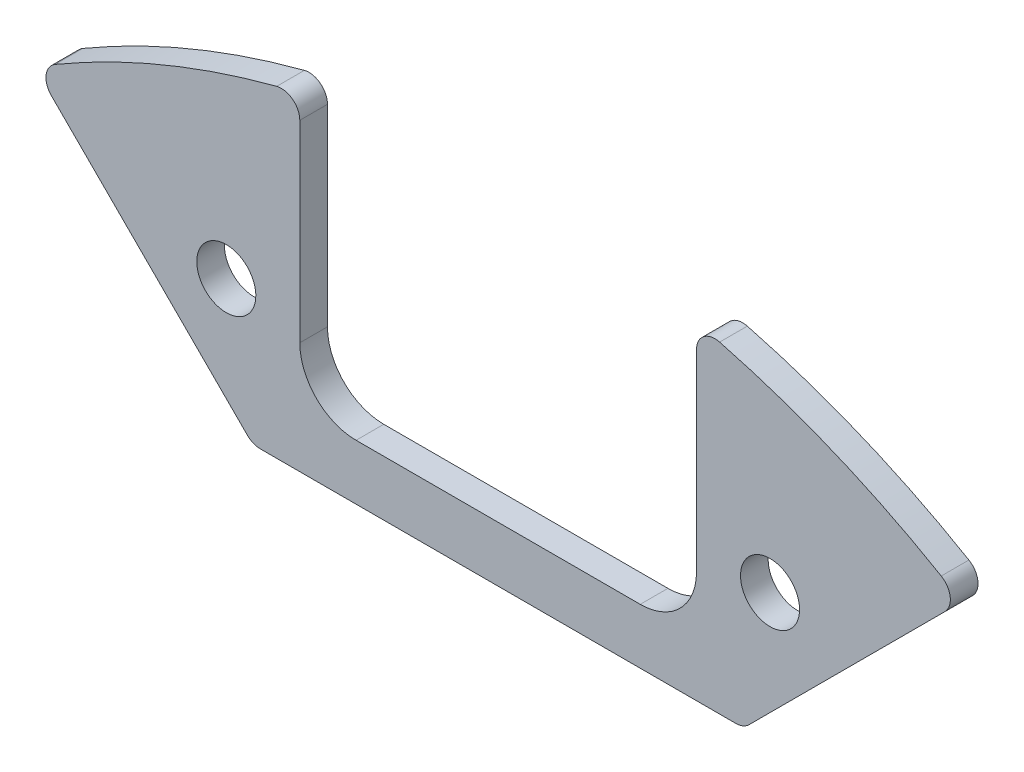
SolidWorks part; units mm, degrees
material "5052-H34"
ref_plane "正面" through (0, 0, 0) normal (0, 0, 1) x (1, 0, 0)
ref_plane "平面" through (0, 0, 0) normal (0, 1, 0) x (1, 0, 0)
ref_plane "右側面" through (0, 0, 0) normal (1, 0, 0) x (0, 0, -1)
sketch "ｽｹｯﾁ1" plane through (0, 0, 0) normal (0, 0, 1) x (1, 0, 0)
  circle A0 centre (0, 0) radius 47.5
  dimension "D1" = 95
extrude "ﾎﾞｽ - 押し出し1" add sketch "ｽｹｯﾁ1" along normal blind 1.5
sketch "ｽｹｯﾁ2" plane through (0, 0, 1.5) normal (0, 0, 1) x (1, 0, 0)
  line L0 (0, 0) -> (0, 47.5) construction
  line L1 (-10.75, 43.525) -> (-10.75, 52.5)
  line L2 (-10.75, 31.5) -> (10.75, 31.5)
  line L3 (-10.75, 31.5) -> (-10.75, 40.475)
  line L4 (-10.75, 52.5) -> (10.75, 52.5)
  line L5 (10.75, 31.5) -> (10.75, 40.475)
  line L6 (-10.75, 31.5) -> (10.75, 52.5) construction
  line L7 (-10.75, 52.5) -> (10.75, 31.5) construction
  line L8 (-13, 43.525) -> (-10.75, 43.525)
  line L9 (-13, 43.525) -> (-13, 40.475)
  line L10 (-13, 40.475) -> (-10.75, 40.475)
  line L11 (13, 43.525) -> (13, 40.475)
  line L12 (-13, 43.525) -> (13, 40.475) construction
  line L13 (-13, 40.475) -> (13, 43.525) construction
  line L14 (10.75, 43.525) -> (10.75, 52.5)
  line L15 (10.75, 43.525) -> (13, 43.525)
  line L17 (10.75, 40.475) -> (13, 40.475)
  circle A0 centre (0, 0) radius 47.5 construction
  point P5 (0, 42)
  point P10 (0, 42)
  dimension "D1" = 42
  dimension "D2" = 21.5
  dimension "D3" = 21
  dimension "D4" = 3.05
  dimension "D5" = 26
extrude "ｶｯﾄ - 押し出し1" cut sketch "ｽｹｯﾁ2" against normal through all
sketch "ｽｹｯﾁ3" plane through (0, 0, 1.5) normal (0, 0, 1) x (1, 0, 0)
  line L1 (-8.8388, -8.8388) -> (8.8388, -8.8388) construction
  line L2 (-8.8388, -8.8388) -> (-8.8388, 8.8388) construction
  line L3 (-8.8388, 8.8388) -> (8.8388, 8.8388) construction
  line L4 (8.8388, -8.8388) -> (8.8388, 8.8388) construction
  line L5 (-8.8388, -8.8388) -> (8.8388, 8.8388) construction
  line L6 (-8.8388, 8.8388) -> (8.8388, -8.8388) construction
  circle A0 centre (0, 0) radius 3.1
  circle A1 centre (0, 0) radius 6.5 construction
  circle A2 centre (0, 6.5) radius 1.6
  circle A3 centre (6.5, 0) radius 1.6
  circle A4 centre (0, -6.5) radius 1.6
  circle A5 centre (-6.5, 0) radius 1.6
  circle A6 centre (0, 0) radius 12.5 construction
  circle A7 centre (8.8388, 8.8388) radius 1.6
  circle A8 centre (8.8388, -8.8388) radius 1.6
  circle A9 centre (-8.8388, -8.8388) radius 1.6
  circle A10 centre (-8.8388, 8.8388) radius 1.6
  dimension "D1" = 6.2
  dimension "D2" = 13
  dimension "D3" = 3.2
  dimension "D5" = 25
  dimension "D6" = 3.2
  dimension "D4" = 4
  dimension "D7" = 4
extrude "ｶｯﾄ - 押し出し2" cut sketch "ｽｹｯﾁ3" against normal through all and the other way through all
sketch "ｽｹｯﾁ4" plane through (0, 0, 1.5) normal (0, 0, 1) x (1, 0, 0)
  line L0 (0, 31.5) -> (0, 0) construction
  line L1 (-10.75, 31.5) -> (10.75, 31.5) construction
  line L2 (0, 0) -> (14.7333, 35.5694) construction
  circle A0 centre (0, 0) radius 22.5 construction
  circle A1 centre (0, 0) radius 38.5 construction
  circle A2 centre (14.7333, 35.5694) radius 1.6
  circle A3 centre (8.6104, 20.7873) radius 1.6
  dimension "D1" = 45
  dimension "D2" = 77
  dimension "D4" = 3.2
  dimension "D3" = 22.5
extrude "ｶｯﾄ - 押し出し3" cut sketch "ｽｹｯﾁ4" against normal through all
sketch "ｽｹｯﾁ5" plane through (0, 0, 1.5) normal (0, 0, 1) x (1, 0, 0)
  line L0 (0, 0) -> (14.7333, 35.5694) construction
  line L1 (-10.75, 31.5) -> (10.75, 31.5) construction
  line L2 (-10.75, 31.5) -> (10.75, 31.5) construction
  line L3 (-7.1883, 26.5) -> (7.1883, 26.5)
  line L4 (-3.3281, 17.1806) -> (-7.1883, 26.5)
  line L5 (0, 31.5) -> (0, 0) construction
  line L6 (-10.75, 26.5) -> (10.75, 26.5) construction
  line L9 (-3.3281, 17.1806) -> (3.3281, 17.1806)
  line L10 (3.3281, 17.1806) -> (7.1883, 26.5)
  circle A0 centre (0, 0) radius 17.5 construction
  dimension "D3" = 35
  dimension "D2" = 7
  dimension "D1" = 5
extrude "ｶｯﾄ - 押し出し4" cut sketch "ｽｹｯﾁ5" against normal through all and the other way through all
fillet "ﾌｨﾚｯﾄ1" radius 1 6 edges at (-3.3281, 17.1806, 0.75) (3.3281, 17.1806, 0.75) (7.1883, 26.5, 0.75) (-7.1883, 26.5, 0.75) (10.75, 46.2676, 0.75) (-10.75, 46.2676, 0.75)
fillet "ﾌｨﾚｯﾄ2" radius 0.2 4 edges at (13, 43.525, 0.75) (13, 40.475, 0.75) (-13, 43.525, 0.75) (-13, 40.475, 0.75)
fillet "ﾌｨﾚｯﾄ3" radius 3.05 2 edges at (10.75, 31.5, 0.75) (-10.75, 31.5, 0.75)
ref_axis "軸1" through (0, 0, 0) along (0, 0, 1)
pattern_circular "円形ﾊﾟﾀｰﾝ1" count 8 over 360 about axis through (0, 0, 0) along (0, 0, 1) of "ｶｯﾄ - 押し出し1", "ﾌｨﾚｯﾄ1", "ｶｯﾄ - 押し出し4", "ｶｯﾄ - 押し出し3", "ﾌｨﾚｯﾄ2", "ﾌｨﾚｯﾄ3"
sketch "ｽｹｯﾁ6" plane through (0, 0, 1.5) normal (0, 0, 1) x (1, 0, 0)
  line L0 (7.7, 28.5) -> (-7.7, 28.5)
  line L1 (-7.7, 28.5) -> (-13.2972, 28.5)
  line L2 (-13.2972, 28.5) -> (-21.0187, 36.2215)
  line L3 (7.7, 28.5) -> (13.2972, 28.5)
  line L4 (25.5973, 14.7078) -> (14.7078, 25.5973)
  line L7 (28.5, -7.7) -> (28.5, 7.7)
  line L10 (14.7078, -25.5973) -> (25.5973, -14.7078)
  line L13 (-7.7, -28.5) -> (7.7, -28.5)
  line L16 (-25.5973, -14.7078) -> (-14.7078, -25.5973)
  line L19 (-28.5, 7.7) -> (-28.5, -7.7)
  line L22 (-14.7078, 25.5973) -> (-25.5973, 14.7078)
  line L23 (13.2972, 28.5) -> (21.0187, 36.2215)
  line L88 (39.4148, 24.212) -> (38.3782, 23.1754)
  line L89 (38.3782, 23.1754) -> (39.8278, 21.7259)
  line L90 (39.8278, 21.443) -> (37.954, 19.5692)
  line L91 (37.6711, 19.5692) -> (36.2215, 21.0187)
  line L92 (36.2215, 21.0187) -> (32.0319, 16.8291)
  line L93 (27.7186, 16.8291) -> (16.8291, 27.7186)
  line L94 (16.8291, 32.0319) -> (21.0187, 36.2215)
  line L95 (21.0187, 36.2215) -> (19.5692, 37.6711)
  line L96 (19.5692, 37.954) -> (21.443, 39.8278)
  line L97 (21.7259, 39.8278) -> (23.1754, 38.3782)
  line L98 (23.1754, 38.3782) -> (24.212, 39.4148)
  line L99 (10.75, 44.991) -> (10.75, 43.525)
  line L100 (10.75, 43.525) -> (12.8, 43.525)
  line L101 (13, 43.325) -> (13, 40.675)
  line L102 (12.8, 40.475) -> (10.75, 40.475)
  line L103 (10.75, 40.475) -> (10.75, 34.55)
  line L104 (7.7, 31.5) -> (-7.7, 31.5)
  line L105 (-10.75, 34.55) -> (-10.75, 40.475)
  line L106 (-10.75, 40.475) -> (-12.8, 40.475)
  line L107 (-13, 40.675) -> (-13, 43.325)
  line L108 (-12.8, 43.525) -> (-10.75, 43.525)
  line L109 (-10.75, 43.525) -> (-10.75, 44.991)
  line L110 (-24.212, 39.4148) -> (-23.1754, 38.3782)
  line L111 (-23.1754, 38.3782) -> (-21.7259, 39.8278)
  line L112 (-21.443, 39.8278) -> (-19.5692, 37.954)
  line L113 (-19.5692, 37.6711) -> (-21.0187, 36.2215)
  line L114 (-21.0187, 36.2215) -> (-16.8291, 32.0319)
  line L115 (-16.8291, 27.7186) -> (-27.7186, 16.8291)
  line L116 (-32.0319, 16.8291) -> (-36.2215, 21.0187)
  line L117 (-36.2215, 21.0187) -> (-37.6711, 19.5692)
  line L118 (-37.954, 19.5692) -> (-39.8278, 21.443)
  line L119 (-39.8278, 21.7259) -> (-38.3782, 23.1754)
  line L120 (-38.3782, 23.1754) -> (-39.4148, 24.212)
  line L121 (-44.991, 10.75) -> (-43.525, 10.75)
  line L122 (-43.525, 10.75) -> (-43.525, 12.8)
  line L123 (-43.325, 13) -> (-40.675, 13)
  line L124 (-40.475, 12.8) -> (-40.475, 10.75)
  line L125 (-40.475, 10.75) -> (-34.55, 10.75)
  line L126 (-31.5, 7.7) -> (-31.5, -7.7)
  line L127 (-34.55, -10.75) -> (-40.475, -10.75)
  line L128 (-40.475, -10.75) -> (-40.475, -12.8)
  line L129 (-40.675, -13) -> (-43.325, -13)
  line L130 (-43.525, -12.8) -> (-43.525, -10.75)
  line L131 (-43.525, -10.75) -> (-44.991, -10.75)
  line L132 (-39.4148, -24.212) -> (-38.3782, -23.1754)
  line L133 (-38.3782, -23.1754) -> (-39.8278, -21.7259)
  line L134 (-39.8278, -21.443) -> (-37.954, -19.5692)
  line L135 (-37.6711, -19.5692) -> (-36.2215, -21.0187)
  line L136 (-36.2215, -21.0187) -> (-32.0319, -16.8291)
  line L137 (-27.7186, -16.8291) -> (-16.8291, -27.7186)
  line L138 (-16.8291, -32.0319) -> (-21.0187, -36.2215)
  line L139 (-21.0187, -36.2215) -> (-19.5692, -37.6711)
  line L140 (-19.5692, -37.954) -> (-21.443, -39.8278)
  line L141 (-21.7259, -39.8278) -> (-23.1754, -38.3782)
  line L142 (-23.1754, -38.3782) -> (-24.212, -39.4148)
  line L143 (-10.75, -44.991) -> (-10.75, -43.525)
  line L144 (-10.75, -43.525) -> (-12.8, -43.525)
  line L145 (-13, -43.325) -> (-13, -40.675)
  line L146 (-12.8, -40.475) -> (-10.75, -40.475)
  line L147 (-10.75, -40.475) -> (-10.75, -34.55)
  line L148 (-7.7, -31.5) -> (7.7, -31.5)
  line L149 (10.75, -34.55) -> (10.75, -40.475)
  line L150 (10.75, -40.475) -> (12.8, -40.475)
  line L151 (13, -40.675) -> (13, -43.325)
  line L152 (12.8, -43.525) -> (10.75, -43.525)
  line L153 (10.75, -43.525) -> (10.75, -44.991)
  line L154 (24.212, -39.4148) -> (23.1754, -38.3782)
  line L155 (23.1754, -38.3782) -> (21.7259, -39.8278)
  line L156 (21.443, -39.8278) -> (19.5692, -37.954)
  line L157 (19.5692, -37.6711) -> (21.0187, -36.2215)
  line L158 (21.0187, -36.2215) -> (16.8291, -32.0319)
  line L159 (16.8291, -27.7186) -> (27.7186, -16.8291)
  line L160 (32.0319, -16.8291) -> (36.2215, -21.0187)
  line L161 (36.2215, -21.0187) -> (37.6711, -19.5692)
  line L162 (37.954, -19.5692) -> (39.8278, -21.443)
  line L163 (39.8278, -21.7259) -> (38.3782, -23.1754)
  line L164 (38.3782, -23.1754) -> (39.4148, -24.212)
  line L165 (44.991, -10.75) -> (43.525, -10.75)
  line L166 (43.525, -10.75) -> (43.525, -12.8)
  line L167 (43.325, -13) -> (40.675, -13)
  line L168 (40.475, -12.8) -> (40.475, -10.75)
  line L169 (40.475, -10.75) -> (34.55, -10.75)
  line L170 (31.5, -7.7) -> (31.5, 7.7)
  line L171 (34.55, 10.75) -> (40.475, 10.75)
  line L172 (40.475, 10.75) -> (40.475, 12.8)
  line L173 (40.675, 13) -> (43.325, 13)
  line L174 (43.525, 12.8) -> (43.525, 10.75)
  line L175 (43.525, 10.75) -> (44.991, 10.75)
  line L176 (39.4148, 24.212) -> (38.3782, 23.1754)
  line L177 (38.3782, 23.1754) -> (39.8278, 21.7259)
  line L178 (39.8278, 21.443) -> (37.954, 19.5692)
  line L179 (37.6711, 19.5692) -> (36.2215, 21.0187)
  line L180 (36.2215, 21.0187) -> (32.0319, 16.8291)
  line L181 (27.7186, 16.8291) -> (16.8291, 27.7186)
  line L182 (16.8291, 32.0319) -> (21.0187, 36.2215)
  line L183 (21.0187, 36.2215) -> (19.5692, 37.6711)
  line L184 (19.5692, 37.954) -> (21.443, 39.8278)
  line L185 (21.7259, 39.8278) -> (23.1754, 38.3782)
  line L186 (23.1754, 38.3782) -> (24.212, 39.4148)
  line L187 (10.75, 44.991) -> (10.75, 43.525)
  line L188 (10.75, 43.525) -> (12.8, 43.525)
  line L189 (13, 43.325) -> (13, 40.675)
  line L190 (12.8, 40.475) -> (10.75, 40.475)
  line L191 (10.75, 40.475) -> (10.75, 34.55)
  line L192 (7.7, 31.5) -> (-7.7, 31.5)
  line L193 (-10.75, 34.55) -> (-10.75, 40.475)
  line L194 (-10.75, 40.475) -> (-12.8, 40.475)
  line L195 (-13, 40.675) -> (-13, 43.325)
  line L196 (-12.8, 43.525) -> (-10.75, 43.525)
  line L197 (-10.75, 43.525) -> (-10.75, 44.991)
  line L198 (-24.212, 39.4148) -> (-23.1754, 38.3782)
  line L199 (-23.1754, 38.3782) -> (-21.7259, 39.8278)
  line L200 (-21.443, 39.8278) -> (-19.5692, 37.954)
  line L201 (-19.5692, 37.6711) -> (-21.0187, 36.2215)
  line L202 (-21.0187, 36.2215) -> (-16.8291, 32.0319)
  line L203 (-16.8291, 27.7186) -> (-27.7186, 16.8291)
  line L204 (-32.0319, 16.8291) -> (-36.2215, 21.0187)
  line L205 (-36.2215, 21.0187) -> (-37.6711, 19.5692)
  line L206 (-37.954, 19.5692) -> (-39.8278, 21.443)
  line L207 (-39.8278, 21.7259) -> (-38.3782, 23.1754)
  line L208 (-38.3782, 23.1754) -> (-39.4148, 24.212)
  line L209 (-44.991, 10.75) -> (-43.525, 10.75)
  line L210 (-43.525, 10.75) -> (-43.525, 12.8)
  line L211 (-43.325, 13) -> (-40.675, 13)
  line L212 (-40.475, 12.8) -> (-40.475, 10.75)
  line L213 (-40.475, 10.75) -> (-34.55, 10.75)
  line L214 (-31.5, 7.7) -> (-31.5, -7.7)
  line L215 (-34.55, -10.75) -> (-40.475, -10.75)
  line L216 (-40.475, -10.75) -> (-40.475, -12.8)
  line L217 (-40.675, -13) -> (-43.325, -13)
  line L218 (-43.525, -12.8) -> (-43.525, -10.75)
  line L219 (-43.525, -10.75) -> (-44.991, -10.75)
  line L220 (-39.4148, -24.212) -> (-38.3782, -23.1754)
  line L221 (-38.3782, -23.1754) -> (-39.8278, -21.7259)
  line L222 (-39.8278, -21.443) -> (-37.954, -19.5692)
  line L223 (-37.6711, -19.5692) -> (-36.2215, -21.0187)
  line L224 (-36.2215, -21.0187) -> (-32.0319, -16.8291)
  line L225 (-27.7186, -16.8291) -> (-16.8291, -27.7186)
  line L226 (-16.8291, -32.0319) -> (-21.0187, -36.2215)
  line L227 (-21.0187, -36.2215) -> (-19.5692, -37.6711)
  line L228 (-19.5692, -37.954) -> (-21.443, -39.8278)
  line L229 (-21.7259, -39.8278) -> (-23.1754, -38.3782)
  line L230 (-23.1754, -38.3782) -> (-24.212, -39.4148)
  line L231 (-10.75, -44.991) -> (-10.75, -43.525)
  line L232 (-10.75, -43.525) -> (-12.8, -43.525)
  line L233 (-13, -43.325) -> (-13, -40.675)
  line L234 (-12.8, -40.475) -> (-10.75, -40.475)
  line L235 (-10.75, -40.475) -> (-10.75, -34.55)
  line L236 (-7.7, -31.5) -> (7.7, -31.5)
  line L237 (10.75, -34.55) -> (10.75, -40.475)
  line L238 (10.75, -40.475) -> (12.8, -40.475)
  line L239 (13, -40.675) -> (13, -43.325)
  line L240 (12.8, -43.525) -> (10.75, -43.525)
  line L241 (10.75, -43.525) -> (10.75, -44.991)
  line L242 (24.212, -39.4148) -> (23.1754, -38.3782)
  line L243 (23.1754, -38.3782) -> (21.7259, -39.8278)
  line L244 (21.443, -39.8278) -> (19.5692, -37.954)
  line L245 (19.5692, -37.6711) -> (21.0187, -36.2215)
  line L246 (21.0187, -36.2215) -> (16.8291, -32.0319)
  line L247 (16.8291, -27.7186) -> (27.7186, -16.8291)
  line L248 (32.0319, -16.8291) -> (36.2215, -21.0187)
  line L249 (36.2215, -21.0187) -> (37.6711, -19.5692)
  line L250 (37.954, -19.5692) -> (39.8278, -21.443)
  line L251 (39.8278, -21.7259) -> (38.3782, -23.1754)
  line L252 (38.3782, -23.1754) -> (39.4148, -24.212)
  line L253 (44.991, -10.75) -> (43.525, -10.75)
  line L254 (43.525, -10.75) -> (43.525, -12.8)
  line L255 (43.325, -13) -> (40.675, -13)
  line L256 (40.475, -12.8) -> (40.475, -10.75)
  line L257 (40.475, -10.75) -> (34.55, -10.75)
  line L258 (31.5, -7.7) -> (31.5, 7.7)
  line L259 (34.55, 10.75) -> (40.475, 10.75)
  line L260 (40.475, 10.75) -> (40.475, 12.8)
  line L261 (40.675, 13) -> (43.325, 13)
  line L262 (43.525, 12.8) -> (43.525, 10.75)
  line L263 (43.525, 10.75) -> (44.991, 10.75)
  arc A72 (45.9585, 12.0027) -> (40.9848, 24.0104) centre (0, 0) ccw
  arc A73 (40.9848, 24.0104) -> (39.4148, 24.212) centre (40.1219, 23.5049) ccw
  arc A74 (39.8278, 21.443) -> (39.8278, 21.7259) centre (39.6864, 21.5844) ccw
  arc A75 (37.6711, 19.5692) -> (37.954, 19.5692) centre (37.8125, 19.7106) ccw
  arc A76 (27.7186, 16.8291) -> (32.0319, 16.8291) centre (29.8753, 18.9858) ccw
  arc A77 (16.8291, 32.0319) -> (16.8291, 27.7186) centre (18.9858, 29.8753) ccw
  arc A78 (19.5692, 37.954) -> (19.5692, 37.6711) centre (19.7106, 37.8125) ccw
  arc A79 (21.7259, 39.8278) -> (21.443, 39.8278) centre (21.5844, 39.6864) ccw
  arc A80 (24.212, 39.4148) -> (24.0104, 40.9848) centre (23.5049, 40.1219) ccw
  arc A81 (24.0104, 40.9848) -> (12.0027, 45.9585) centre (0, 0) ccw
  arc A82 (12.0027, 45.9585) -> (10.75, 44.991) centre (11.75, 44.991) ccw
  arc A83 (13, 43.325) -> (12.8, 43.525) centre (12.8, 43.325) ccw
  arc A84 (12.8, 40.475) -> (13, 40.675) centre (12.8, 40.675) ccw
  arc A85 (7.7, 31.5) -> (10.75, 34.55) centre (7.7, 34.55) ccw
  arc A86 (-10.75, 34.55) -> (-7.7, 31.5) centre (-7.7, 34.55) ccw
  arc A87 (-13, 40.675) -> (-12.8, 40.475) centre (-12.8, 40.675) ccw
  arc A88 (-12.8, 43.525) -> (-13, 43.325) centre (-12.8, 43.325) ccw
  arc A89 (-10.75, 44.991) -> (-12.0027, 45.9585) centre (-11.75, 44.991) ccw
  arc A90 (-12.0027, 45.9585) -> (-24.0104, 40.9848) centre (0, 0) ccw
  arc A91 (-24.0104, 40.9848) -> (-24.212, 39.4148) centre (-23.5049, 40.1219) ccw
  arc A92 (-21.443, 39.8278) -> (-21.7259, 39.8278) centre (-21.5844, 39.6864) ccw
  arc A93 (-19.5692, 37.6711) -> (-19.5692, 37.954) centre (-19.7106, 37.8125) ccw
  arc A94 (-16.8291, 27.7186) -> (-16.8291, 32.0319) centre (-18.9858, 29.8753) ccw
  arc A95 (-32.0319, 16.8291) -> (-27.7186, 16.8291) centre (-29.8753, 18.9858) ccw
  arc A96 (-37.954, 19.5692) -> (-37.6711, 19.5692) centre (-37.8125, 19.7106) ccw
  arc A97 (-39.8278, 21.7259) -> (-39.8278, 21.443) centre (-39.6864, 21.5844) ccw
  arc A98 (-39.4148, 24.212) -> (-40.9848, 24.0104) centre (-40.1219, 23.5049) ccw
  arc A99 (-40.9848, 24.0104) -> (-45.9585, 12.0027) centre (0, 0) ccw
  arc A100 (-45.9585, 12.0027) -> (-44.991, 10.75) centre (-44.991, 11.75) ccw
  arc A101 (-43.325, 13) -> (-43.525, 12.8) centre (-43.325, 12.8) ccw
  arc A102 (-40.475, 12.8) -> (-40.675, 13) centre (-40.675, 12.8) ccw
  arc A103 (-31.5, 7.7) -> (-34.55, 10.75) centre (-34.55, 7.7) ccw
  arc A104 (-34.55, -10.75) -> (-31.5, -7.7) centre (-34.55, -7.7) ccw
  arc A105 (-40.675, -13) -> (-40.475, -12.8) centre (-40.675, -12.8) ccw
  arc A106 (-43.525, -12.8) -> (-43.325, -13) centre (-43.325, -12.8) ccw
  arc A107 (-44.991, -10.75) -> (-45.9585, -12.0027) centre (-44.991, -11.75) ccw
  arc A108 (-45.9585, -12.0027) -> (-40.9848, -24.0104) centre (0, 0) ccw
  arc A109 (-40.9848, -24.0104) -> (-39.4148, -24.212) centre (-40.1219, -23.5049) ccw
  arc A110 (-39.8278, -21.443) -> (-39.8278, -21.7259) centre (-39.6864, -21.5844) ccw
  arc A111 (-37.6711, -19.5692) -> (-37.954, -19.5692) centre (-37.8125, -19.7106) ccw
  arc A112 (-27.7186, -16.8291) -> (-32.0319, -16.8291) centre (-29.8753, -18.9858) ccw
  arc A113 (-16.8291, -32.0319) -> (-16.8291, -27.7186) centre (-18.9858, -29.8753) ccw
  arc A114 (-19.5692, -37.954) -> (-19.5692, -37.6711) centre (-19.7106, -37.8125) ccw
  arc A115 (-21.7259, -39.8278) -> (-21.443, -39.8278) centre (-21.5844, -39.6864) ccw
  arc A116 (-24.212, -39.4148) -> (-24.0104, -40.9848) centre (-23.5049, -40.1219) ccw
  arc A117 (-24.0104, -40.9848) -> (-12.0027, -45.9585) centre (0, 0) ccw
  arc A118 (-12.0027, -45.9585) -> (-10.75, -44.991) centre (-11.75, -44.991) ccw
  arc A119 (-13, -43.325) -> (-12.8, -43.525) centre (-12.8, -43.325) ccw
  arc A120 (-12.8, -40.475) -> (-13, -40.675) centre (-12.8, -40.675) ccw
  arc A121 (-7.7, -31.5) -> (-10.75, -34.55) centre (-7.7, -34.55) ccw
  arc A122 (10.75, -34.55) -> (7.7, -31.5) centre (7.7, -34.55) ccw
  arc A123 (13, -40.675) -> (12.8, -40.475) centre (12.8, -40.675) ccw
  arc A124 (12.8, -43.525) -> (13, -43.325) centre (12.8, -43.325) ccw
  arc A125 (10.75, -44.991) -> (12.0027, -45.9585) centre (11.75, -44.991) ccw
  arc A126 (12.0027, -45.9585) -> (24.0104, -40.9848) centre (0, 0) ccw
  arc A127 (24.0104, -40.9848) -> (24.212, -39.4148) centre (23.5049, -40.1219) ccw
  arc A128 (21.443, -39.8278) -> (21.7259, -39.8278) centre (21.5844, -39.6864) ccw
  arc A129 (19.5692, -37.6711) -> (19.5692, -37.954) centre (19.7106, -37.8125) ccw
  arc A130 (16.8291, -27.7186) -> (16.8291, -32.0319) centre (18.9858, -29.8753) ccw
  arc A131 (32.0319, -16.8291) -> (27.7186, -16.8291) centre (29.8753, -18.9858) ccw
  arc A132 (37.954, -19.5692) -> (37.6711, -19.5692) centre (37.8125, -19.7106) ccw
  arc A133 (39.8278, -21.7259) -> (39.8278, -21.443) centre (39.6864, -21.5844) ccw
  arc A134 (39.4148, -24.212) -> (40.9848, -24.0104) centre (40.1219, -23.5049) ccw
  arc A135 (40.9848, -24.0104) -> (45.9585, -12.0027) centre (0, 0) ccw
  arc A136 (45.9585, -12.0027) -> (44.991, -10.75) centre (44.991, -11.75) ccw
  arc A137 (43.325, -13) -> (43.525, -12.8) centre (43.325, -12.8) ccw
  arc A138 (40.475, -12.8) -> (40.675, -13) centre (40.675, -12.8) ccw
  arc A139 (31.5, -7.7) -> (34.55, -10.75) centre (34.55, -7.7) ccw
  arc A140 (34.55, 10.75) -> (31.5, 7.7) centre (34.55, 7.7) ccw
  arc A141 (40.675, 13) -> (40.475, 12.8) centre (40.675, 12.8) ccw
  arc A142 (43.525, 12.8) -> (43.325, 13) centre (43.325, 12.8) ccw
  arc A143 (44.991, 10.75) -> (45.9585, 12.0027) centre (44.991, 11.75) ccw
  arc A144 (45.9585, 12.0027) -> (40.9848, 24.0104) centre (0, 0) ccw
  arc A145 (40.9848, 24.0104) -> (39.4148, 24.212) centre (40.1219, 23.5049) ccw
  arc A146 (39.8278, 21.443) -> (39.8278, 21.7259) centre (39.6864, 21.5844) ccw
  arc A147 (37.6711, 19.5692) -> (37.954, 19.5692) centre (37.8125, 19.7106) ccw
  arc A148 (27.7186, 16.8291) -> (32.0319, 16.8291) centre (29.8753, 18.9858) ccw
  arc A149 (16.8291, 32.0319) -> (16.8291, 27.7186) centre (18.9858, 29.8753) ccw
  arc A150 (19.5692, 37.954) -> (19.5692, 37.6711) centre (19.7106, 37.8125) ccw
  arc A151 (21.7259, 39.8278) -> (21.443, 39.8278) centre (21.5844, 39.6864) ccw
  arc A152 (24.212, 39.4148) -> (24.0104, 40.9848) centre (23.5049, 40.1219) ccw
  arc A153 (24.0104, 40.9848) -> (12.0027, 45.9585) centre (0, 0) ccw
  arc A154 (12.0027, 45.9585) -> (10.75, 44.991) centre (11.75, 44.991) ccw
  arc A155 (13, 43.325) -> (12.8, 43.525) centre (12.8, 43.325) ccw
  arc A156 (12.8, 40.475) -> (13, 40.675) centre (12.8, 40.675) ccw
  arc A157 (7.7, 31.5) -> (10.75, 34.55) centre (7.7, 34.55) ccw
  arc A158 (-10.75, 34.55) -> (-7.7, 31.5) centre (-7.7, 34.55) ccw
  arc A159 (-13, 40.675) -> (-12.8, 40.475) centre (-12.8, 40.675) ccw
  arc A160 (-12.8, 43.525) -> (-13, 43.325) centre (-12.8, 43.325) ccw
  arc A161 (-10.75, 44.991) -> (-12.0027, 45.9585) centre (-11.75, 44.991) ccw
  arc A162 (-12.0027, 45.9585) -> (-24.0104, 40.9848) centre (0, 0) ccw
  arc A163 (-24.0104, 40.9848) -> (-24.212, 39.4148) centre (-23.5049, 40.1219) ccw
  arc A164 (-21.443, 39.8278) -> (-21.7259, 39.8278) centre (-21.5844, 39.6864) ccw
  arc A165 (-19.5692, 37.6711) -> (-19.5692, 37.954) centre (-19.7106, 37.8125) ccw
  arc A166 (-16.8291, 27.7186) -> (-16.8291, 32.0319) centre (-18.9858, 29.8753) ccw
  arc A167 (-32.0319, 16.8291) -> (-27.7186, 16.8291) centre (-29.8753, 18.9858) ccw
  arc A168 (-37.954, 19.5692) -> (-37.6711, 19.5692) centre (-37.8125, 19.7106) ccw
  arc A169 (-39.8278, 21.7259) -> (-39.8278, 21.443) centre (-39.6864, 21.5844) ccw
  arc A170 (-39.4148, 24.212) -> (-40.9848, 24.0104) centre (-40.1219, 23.5049) ccw
  arc A171 (-40.9848, 24.0104) -> (-45.9585, 12.0027) centre (0, 0) ccw
  arc A172 (-45.9585, 12.0027) -> (-44.991, 10.75) centre (-44.991, 11.75) ccw
  arc A173 (-43.325, 13) -> (-43.525, 12.8) centre (-43.325, 12.8) ccw
  arc A174 (-40.475, 12.8) -> (-40.675, 13) centre (-40.675, 12.8) ccw
  arc A175 (-31.5, 7.7) -> (-34.55, 10.75) centre (-34.55, 7.7) ccw
  arc A176 (-34.55, -10.75) -> (-31.5, -7.7) centre (-34.55, -7.7) ccw
  arc A177 (-40.675, -13) -> (-40.475, -12.8) centre (-40.675, -12.8) ccw
  arc A178 (-43.525, -12.8) -> (-43.325, -13) centre (-43.325, -12.8) ccw
  arc A179 (-44.991, -10.75) -> (-45.9585, -12.0027) centre (-44.991, -11.75) ccw
  arc A180 (-45.9585, -12.0027) -> (-40.9848, -24.0104) centre (0, 0) ccw
  arc A181 (-40.9848, -24.0104) -> (-39.4148, -24.212) centre (-40.1219, -23.5049) ccw
  arc A182 (-39.8278, -21.443) -> (-39.8278, -21.7259) centre (-39.6864, -21.5844) ccw
  arc A183 (-37.6711, -19.5692) -> (-37.954, -19.5692) centre (-37.8125, -19.7106) ccw
  arc A184 (-27.7186, -16.8291) -> (-32.0319, -16.8291) centre (-29.8753, -18.9858) ccw
  arc A185 (-16.8291, -32.0319) -> (-16.8291, -27.7186) centre (-18.9858, -29.8753) ccw
  arc A186 (-19.5692, -37.954) -> (-19.5692, -37.6711) centre (-19.7106, -37.8125) ccw
  arc A187 (-21.7259, -39.8278) -> (-21.443, -39.8278) centre (-21.5844, -39.6864) ccw
  arc A188 (-24.212, -39.4148) -> (-24.0104, -40.9848) centre (-23.5049, -40.1219) ccw
  arc A189 (-24.0104, -40.9848) -> (-12.0027, -45.9585) centre (0, 0) ccw
  arc A190 (-12.0027, -45.9585) -> (-10.75, -44.991) centre (-11.75, -44.991) ccw
  arc A191 (-13, -43.325) -> (-12.8, -43.525) centre (-12.8, -43.325) ccw
  arc A192 (-12.8, -40.475) -> (-13, -40.675) centre (-12.8, -40.675) ccw
  arc A193 (-7.7, -31.5) -> (-10.75, -34.55) centre (-7.7, -34.55) ccw
  arc A194 (10.75, -34.55) -> (7.7, -31.5) centre (7.7, -34.55) ccw
  arc A195 (13, -40.675) -> (12.8, -40.475) centre (12.8, -40.675) ccw
  arc A196 (12.8, -43.525) -> (13, -43.325) centre (12.8, -43.325) ccw
  arc A197 (10.75, -44.991) -> (12.0027, -45.9585) centre (11.75, -44.991) ccw
  arc A198 (12.0027, -45.9585) -> (24.0104, -40.9848) centre (0, 0) ccw
  arc A199 (24.0104, -40.9848) -> (24.212, -39.4148) centre (23.5049, -40.1219) ccw
  arc A200 (21.443, -39.8278) -> (21.7259, -39.8278) centre (21.5844, -39.6864) ccw
  arc A201 (19.5692, -37.6711) -> (19.5692, -37.954) centre (19.7106, -37.8125) ccw
  arc A202 (16.8291, -27.7186) -> (16.8291, -32.0319) centre (18.9858, -29.8753) ccw
  arc A203 (32.0319, -16.8291) -> (27.7186, -16.8291) centre (29.8753, -18.9858) ccw
  arc A204 (37.954, -19.5692) -> (37.6711, -19.5692) centre (37.8125, -19.7106) ccw
  arc A205 (39.8278, -21.7259) -> (39.8278, -21.443) centre (39.6864, -21.5844) ccw
  arc A206 (39.4148, -24.212) -> (40.9848, -24.0104) centre (40.1219, -23.5049) ccw
  arc A207 (40.9848, -24.0104) -> (45.9585, -12.0027) centre (0, 0) ccw
  arc A208 (45.9585, -12.0027) -> (44.991, -10.75) centre (44.991, -11.75) ccw
  arc A209 (43.325, -13) -> (43.525, -12.8) centre (43.325, -12.8) ccw
  arc A210 (40.475, -12.8) -> (40.675, -13) centre (40.675, -12.8) ccw
  arc A211 (31.5, -7.7) -> (34.55, -10.75) centre (34.55, -7.7) ccw
  arc A212 (34.55, 10.75) -> (31.5, 7.7) centre (34.55, 7.7) ccw
  arc A213 (40.675, 13) -> (40.475, 12.8) centre (40.675, 12.8) ccw
  arc A214 (43.525, 12.8) -> (43.325, 13) centre (43.325, 12.8) ccw
  arc A215 (44.991, 10.75) -> (45.9585, 12.0027) centre (44.991, 11.75) ccw
  dimension "D4" = 3
  dimension "D5" = 3
  dimension "D1" = 0
  dimension "D2" = 3
  dimension "D3" = 8
extrude "ｶｯﾄ - 押し出し5" cut sketch "ｽｹｯﾁ6" against normal through all contours L22 L19 L16 L13 L10 L7 L4 L0 region at (0, -3.0739, 1.5)
sketch "ｽｹｯﾁ7" plane through (0, 0, 1.5) normal (0, 0, 1) x (1, 0, 0)
  line L0 (-10.75, 43.525) -> (-10.75, 40.475)
  line L1 (10.75, 43.525) -> (10.75, 40.475)
  line L2 (23.1754, 38.3782) -> (21.0187, 36.2215)
  line L15 (-23.1754, 38.3782) -> (-21.0187, 36.2215)
  line L38 (-13.2972, 28.5) -> (13.2972, 28.5)
  line L39 (-13.2972, 28.5) -> (13.2972, 28.5)
  line L94 (13.2972, 28.5) -> (21.0187, 36.2215)
  line L95 (21.0187, 36.2215) -> (19.5692, 37.6711)
  line L96 (19.5692, 37.954) -> (21.443, 39.8278)
  line L97 (21.7259, 39.8278) -> (23.1754, 38.3782)
  line L98 (23.1754, 38.3782) -> (24.212, 39.4148)
  line L99 (10.75, 44.991) -> (10.75, 43.525)
  line L100 (10.75, 43.525) -> (12.8, 43.525)
  line L101 (13, 43.325) -> (13, 40.675)
  line L102 (12.8, 40.475) -> (10.75, 40.475)
  line L103 (10.75, 40.475) -> (10.75, 34.55)
  line L104 (7.7, 31.5) -> (-7.7, 31.5)
  line L105 (-10.75, 34.55) -> (-10.75, 40.475)
  line L106 (-10.75, 40.475) -> (-12.8, 40.475)
  line L107 (-13, 40.675) -> (-13, 43.325)
  line L108 (-12.8, 43.525) -> (-10.75, 43.525)
  line L109 (-10.75, 43.525) -> (-10.75, 44.991)
  line L110 (-24.212, 39.4148) -> (-23.1754, 38.3782)
  line L111 (-23.1754, 38.3782) -> (-21.7259, 39.8278)
  line L112 (-21.443, 39.8278) -> (-19.5692, 37.954)
  line L113 (-19.5692, 37.6711) -> (-21.0187, 36.2215)
  line L114 (-21.0187, 36.2215) -> (-13.2972, 28.5)
  line L182 (13.2972, 28.5) -> (21.0187, 36.2215)
  line L183 (21.0187, 36.2215) -> (19.5692, 37.6711)
  line L184 (19.5692, 37.954) -> (21.443, 39.8278)
  line L185 (21.7259, 39.8278) -> (23.1754, 38.3782)
  line L186 (23.1754, 38.3782) -> (24.212, 39.4148)
  line L187 (10.75, 44.991) -> (10.75, 43.525)
  line L188 (10.75, 43.525) -> (12.8, 43.525)
  line L189 (13, 43.325) -> (13, 40.675)
  line L190 (12.8, 40.475) -> (10.75, 40.475)
  line L191 (10.75, 40.475) -> (10.75, 34.55)
  line L192 (7.7, 31.5) -> (-7.7, 31.5)
  line L193 (-10.75, 34.55) -> (-10.75, 40.475)
  line L194 (-10.75, 40.475) -> (-12.8, 40.475)
  line L195 (-13, 40.675) -> (-13, 43.325)
  line L196 (-12.8, 43.525) -> (-10.75, 43.525)
  line L197 (-10.75, 43.525) -> (-10.75, 44.991)
  line L198 (-24.212, 39.4148) -> (-23.1754, 38.3782)
  line L199 (-23.1754, 38.3782) -> (-21.7259, 39.8278)
  line L200 (-21.443, 39.8278) -> (-19.5692, 37.954)
  line L201 (-19.5692, 37.6711) -> (-21.0187, 36.2215)
  line L202 (-21.0187, 36.2215) -> (-13.2972, 28.5)
  line L203 (-38.3782, -23.1754) -> (-36.2215, -21.0187)
  line L204 (-43.525, -10.75) -> (-40.475, -10.75)
  line L205 (-43.525, 10.75) -> (-40.475, 10.75)
  line L206 (-38.3782, 23.1754) -> (-36.2215, 21.0187)
  line L207 (43.525, -10.75) -> (40.475, -10.75)
  line L208 (38.3782, -23.1754) -> (36.2215, -21.0187)
  line L209 (23.1754, -38.3782) -> (21.0187, -36.2215)
  line L210 (10.75, -43.525) -> (10.75, -40.475)
  line L211 (-10.75, -43.525) -> (-10.75, -40.475)
  line L212 (-23.1754, -38.3782) -> (-21.0187, -36.2215)
  line L213 (38.3782, 23.1754) -> (36.2215, 21.0187)
  line L214 (43.525, 10.75) -> (40.475, 10.75)
  arc A78 (19.5692, 37.954) -> (19.5692, 37.6711) centre (19.7106, 37.8125) ccw
  arc A79 (21.7259, 39.8278) -> (21.443, 39.8278) centre (21.5844, 39.6864) ccw
  arc A80 (24.212, 39.4148) -> (24.0104, 40.9848) centre (23.5049, 40.1219) ccw
  arc A81 (24.0104, 40.9848) -> (12.0027, 45.9585) centre (0, 0) ccw
  arc A82 (12.0027, 45.9585) -> (10.75, 44.991) centre (11.75, 44.991) ccw
  arc A83 (13, 43.325) -> (12.8, 43.525) centre (12.8, 43.325) ccw
  arc A84 (12.8, 40.475) -> (13, 40.675) centre (12.8, 40.675) ccw
  arc A85 (7.7, 31.5) -> (10.75, 34.55) centre (7.7, 34.55) ccw
  arc A86 (-10.75, 34.55) -> (-7.7, 31.5) centre (-7.7, 34.55) ccw
  arc A87 (-13, 40.675) -> (-12.8, 40.475) centre (-12.8, 40.675) ccw
  arc A88 (-12.8, 43.525) -> (-13, 43.325) centre (-12.8, 43.325) ccw
  arc A89 (-10.75, 44.991) -> (-12.0027, 45.9585) centre (-11.75, 44.991) ccw
  arc A90 (-12.0027, 45.9585) -> (-24.0104, 40.9848) centre (0, 0) ccw
  arc A91 (-24.0104, 40.9848) -> (-24.212, 39.4148) centre (-23.5049, 40.1219) ccw
  arc A92 (-21.443, 39.8278) -> (-21.7259, 39.8278) centre (-21.5844, 39.6864) ccw
  arc A93 (-19.5692, 37.6711) -> (-19.5692, 37.954) centre (-19.7106, 37.8125) ccw
  arc A150 (19.5692, 37.954) -> (19.5692, 37.6711) centre (19.7106, 37.8125) ccw
  arc A151 (21.7259, 39.8278) -> (21.443, 39.8278) centre (21.5844, 39.6864) ccw
  arc A152 (24.212, 39.4148) -> (24.0104, 40.9848) centre (23.5049, 40.1219) ccw
  arc A153 (24.0104, 40.9848) -> (12.0027, 45.9585) centre (0, 0) ccw
  arc A154 (12.0027, 45.9585) -> (10.75, 44.991) centre (11.75, 44.991) ccw
  arc A155 (13, 43.325) -> (12.8, 43.525) centre (12.8, 43.325) ccw
  arc A156 (12.8, 40.475) -> (13, 40.675) centre (12.8, 40.675) ccw
  arc A157 (7.7, 31.5) -> (10.75, 34.55) centre (7.7, 34.55) ccw
  arc A158 (-10.75, 34.55) -> (-7.7, 31.5) centre (-7.7, 34.55) ccw
  arc A159 (-13, 40.675) -> (-12.8, 40.475) centre (-12.8, 40.675) ccw
  arc A160 (-12.8, 43.525) -> (-13, 43.325) centre (-12.8, 43.325) ccw
  arc A161 (-10.75, 44.991) -> (-12.0027, 45.9585) centre (-11.75, 44.991) ccw
  arc A162 (-12.0027, 45.9585) -> (-24.0104, 40.9848) centre (0, 0) ccw
  arc A163 (-24.0104, 40.9848) -> (-24.212, 39.4148) centre (-23.5049, 40.1219) ccw
  arc A164 (-21.443, 39.8278) -> (-21.7259, 39.8278) centre (-21.5844, 39.6864) ccw
  arc A165 (-19.5692, 37.6711) -> (-19.5692, 37.954) centre (-19.7106, 37.8125) ccw
  line M340 (21.0187, 36.2215) -> (19.5692, 37.6711)
  arc M341 (19.5692, 37.6711) -> (19.5692, 37.954) centre (19.7106, 37.8125) cw
  line M342 (19.5692, 37.954) -> (21.443, 39.8278)
  arc M343 (21.443, 39.8278) -> (21.7259, 39.8278) centre (21.5844, 39.6864) cw
  line M344 (21.7259, 39.8278) -> (23.1754, 38.3782)
  line M370 (-23.1754, 38.3782) -> (-21.7259, 39.8278)
  arc M371 (-21.7259, 39.8278) -> (-21.443, 39.8278) centre (-21.5844, 39.6864) cw
  line M372 (-21.443, 39.8278) -> (-19.5692, 37.954)
  arc M373 (-19.5692, 37.954) -> (-19.5692, 37.6711) centre (-19.7106, 37.8125) cw
  line M374 (-19.5692, 37.6711) -> (-21.0187, 36.2215)
  dimension "D1" = 0
  dimension "D2" = 8
extrude "ﾎﾞｽ - 押し出し2" add sketch "ｽｹｯﾁ7" against normal blind 1.5 contours L196 A160 L195 A159 L194 L0 | L190 A156 L189 A155 L188 L1 | L15 M370 M374 M373 M372 M371 | L2 M344 M343 M342 M341 M340 region at (-11.8723, 42, 1.5) region at (-21.3035, 38.0935, 1.5) region at (11.8723, 42, 1.5) region at (21.3035, 38.0935, 1.5)
fillet "ﾌｨﾚｯﾄ4" radius 1 2 edges at (13.2972, 28.5, 0.75) (-13.2972, 28.5, 0.75)
